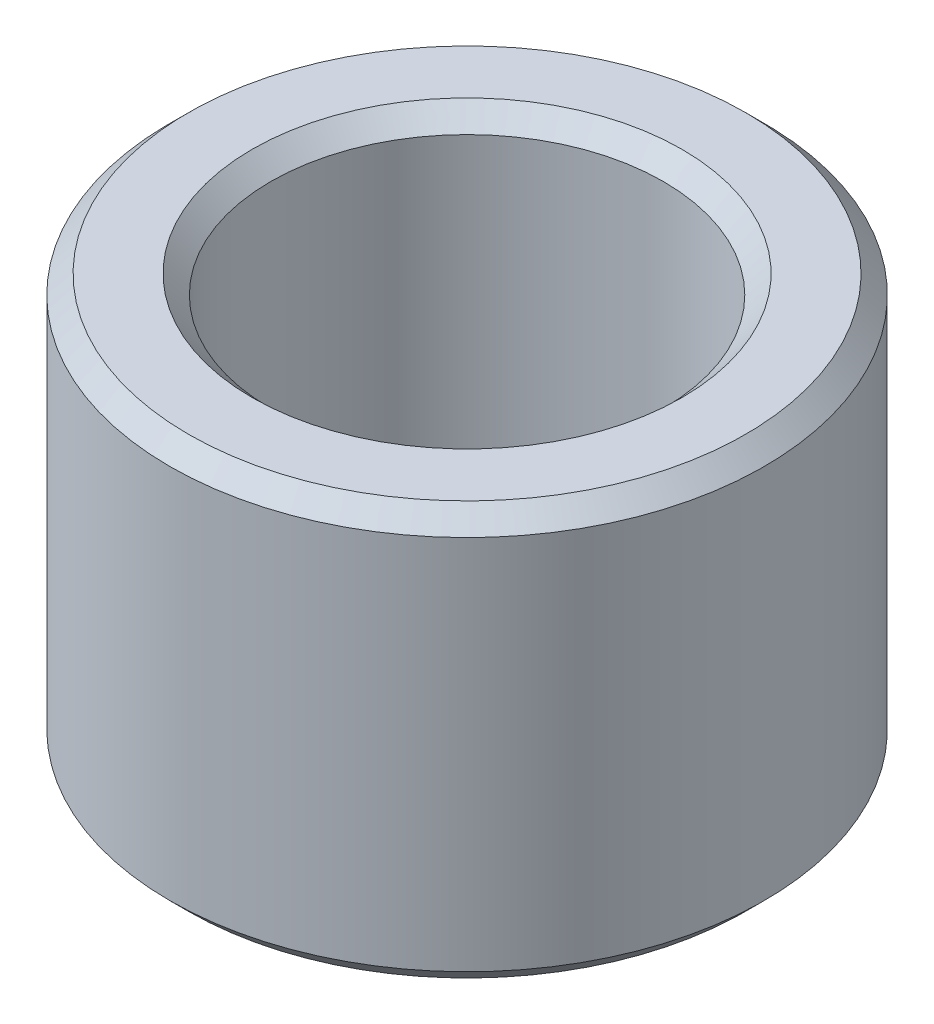
SolidWorks part; units mm, degrees
ref_plane "Front Plane" through (0, 0, 0) normal (0, 0, 1) x (1, 0, 0)
ref_plane "Top Plane" through (0, 0, 0) normal (0, 1, 0) x (1, 0, 0)
ref_plane "Right Plane" through (0, 0, 0) normal (1, 0, 0) x (0, 0, -1)
sketch "Sketch1" plane through (0, 0, 0) normal (0, 1, 0) x (1, 0, 0)
  circle A0 centre (0, 0) radius 40
  dimension "SLEEVE_OD" = 80
extrude "Boss-Extrude1" add sketch "Sketch1" along normal blind 55.6094
sketch "Sketch2" plane through (0, 0, 0) normal (0, 1, 0) x (1, 0, 0)
  circle A0 centre (0, 0) radius 26.4318
  dimension "BORE_D" = 52.8637
extrude "Cut-Extrude1" cut sketch "Sketch2" along normal through all
chamfer "Chamfer1" distance 2.5027 angle 45 4 edges at (0, 55.6094, 26.4318) (0, 0, 26.4318) (0, 0, 40) (0, 55.6094, 40)
